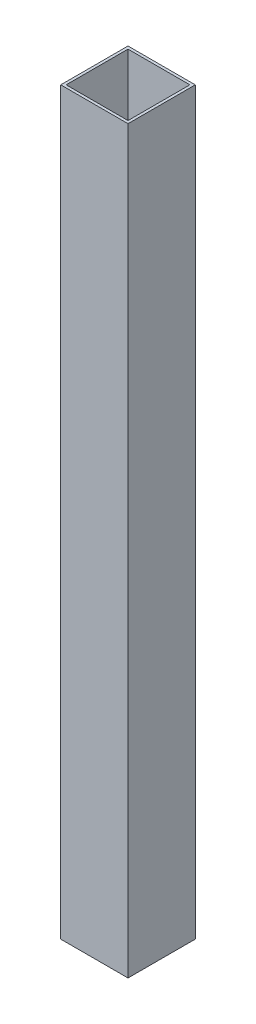
SolidWorks part; units mm, degrees
material "6061 Alloy"
ref_plane "Front Plane" through (0, 0, 0) normal (0, 0, 1) x (1, 0, 0)
ref_plane "Top Plane" through (0, 0, 0) normal (0, 1, 0) x (1, 0, 0)
ref_plane "Right Plane" through (0, 0, 0) normal (1, 0, 0) x (0, 0, -1)
sketch "Sketch1" plane through (0, 0, 0) normal (0, 1, 0) x (1, 0, 0)
  line L1 (19.05, 19.05) -> (-19.05, 19.05)
  line L2 (19.05, 19.05) -> (19.05, -19.05)
  line L3 (19.05, -19.05) -> (-19.05, -19.05)
  line L4 (-19.05, 19.05) -> (-19.05, -19.05)
  line L5 (19.05, 19.05) -> (-19.05, -19.05) construction
  line L6 (19.05, -19.05) -> (-19.05, 19.05) construction
  point P0 (0, 0)
  dimension "D1" = 38.1
extrude "Extrude-Thin1" add sketch "Sketch1" along normal blind 419.1 thin thin type one direction reverse wall 1.524
